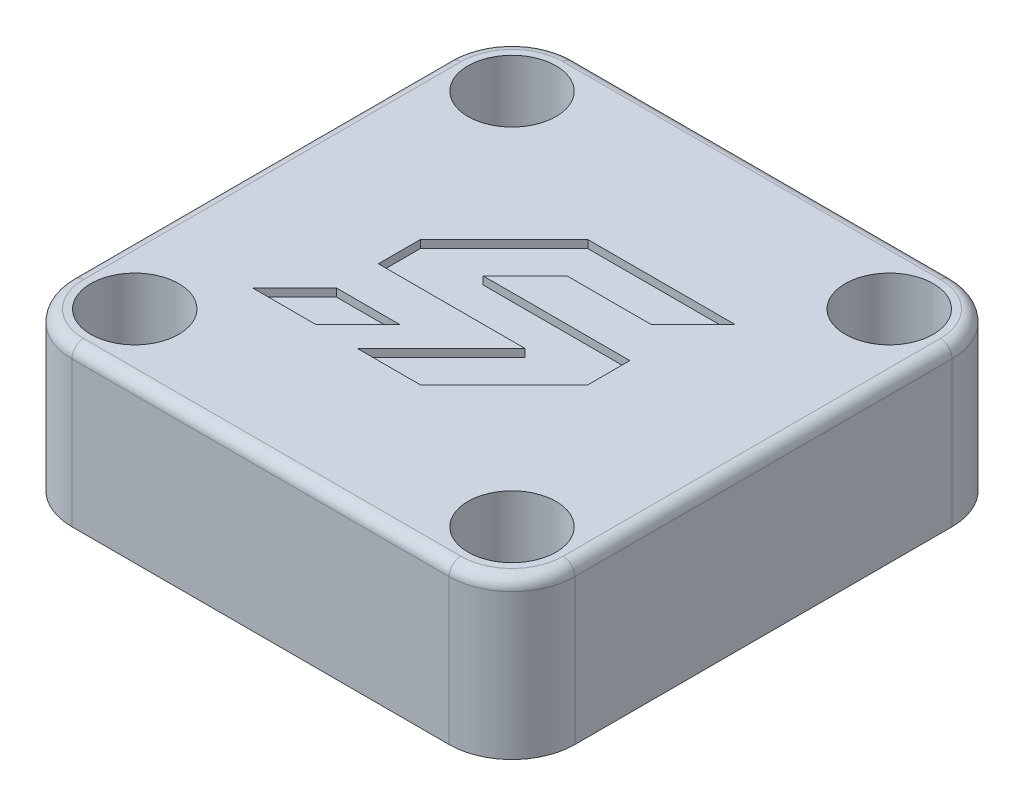
SolidWorks part; units mm, degrees
ref_plane "Front Plane" through (0, 0, 0) normal (0, 0, 1) x (1, 0, 0)
ref_plane "Top Plane" through (0, 0, 0) normal (0, 1, 0) x (1, 0, 0)
ref_plane "Right Plane" through (0, 0, 0) normal (1, 0, 0) x (0, 0, -1)
sketch "Sketch1" plane through (0, 0, 0) normal (0, 1, 0) x (1, 0, 0)
  line L0 (-16, 12) -> (-16, -12)
  line L1 (-12, 12) -> (12, 12)
  line L2 (-12, 12) -> (-12, -12)
  line L3 (-12, -12) -> (12, -12)
  line L4 (12, 12) -> (12, -12)
  line L5 (-12, 12) -> (12, -12) construction
  line L6 (-12, -12) -> (12, 12) construction
  line L7 (-12, -16) -> (12, -16)
  line L8 (16, 12) -> (16, -12)
  line L9 (-12, 16) -> (12, 16)
  circle A0 centre (-12, 12) radius 1.6
  circle A1 centre (12, 12) radius 1.6
  circle A2 centre (12, -12) radius 1.6
  circle A3 centre (-12, -12) radius 1.6
  circle A4 centre (-12, 12) radius 4
  circle A5 centre (12, 12) radius 4
  circle A6 centre (12, -12) radius 4
  circle A7 centre (-12, -12) radius 4
  point P0 (0, 0)
  dimension "D2" = 3.2
  dimension "D3" = 8
  dimension "D1" = 24
extrude "Boss-Extrude1" add sketch "Sketch1" along normal blind 10 contours A5 L9 A4 L1 | L1 A4 L2 A0 | A7 L2 A4 L0 | A7 L3 A3 L2 | A7 L7 A6 L3 | A6 L4 A2 L3 | A6 L8 A5 L4 | A7 L3 A6 L4 A5 L1 A4 L2 | L4 A6 L3 A2 | L3 A7 L2 A3 | L2 A4 L1 A0 | L4 A5 L1 A1 | L1 A5 L4 A1 region at (-14.1072, 0, 0) region at (-14.7484, 0, -14.7484) region at (-14.7484, 0, 9.2516) region at (0, 0, -14.1072) region at (0, 0, 0) region at (-10.1083, 0, -10.1083) region at (0, 0, 14.1072) region at (-10.1083, 0, 10.1083) region at (14.7484, 0, -14.7484) region at (9.2516, 0, 14.7484) region at (14.1072, 0, 0) region at (10.1083, 0, -10.1083) region at (10.1083, 0, 10.1083)
sketch "Sketch2" plane through (0, 0, 0) normal (0, -1, 0) x (1, 0, 0)
  line L0 (-12, 16) -> (12, 16) construction
  line L1 (8, -16) -> (-8, -16)
  line L2 (8, -16) -> (8, 16)
  line L3 (8, 16) -> (-8, 16)
  line L4 (-8, -16) -> (-8, 16)
  line L5 (8, -16) -> (-8, 16) construction
  line L6 (8, 16) -> (-8, -16) construction
  circle A0 centre (0, 0) radius 14
  circle A3 centre (-12, 12) radius 1.6 construction
  circle A4 centre (-12, 12) radius 1.6
  line M12 (-12, -16) -> (12, -16)
  dimension "D1" = 28
  dimension "D2" = 4
extrude "Cut-Extrude1" cut sketch "Sketch2" against normal offset from surface (8.5 mm away) 1.5 contours A0 L4 L2 M12 | A0 region at (0, 0, -14.5009) up to face at (-12, 10, 13.6)
sketch "Sketch3" plane through (0, 10, 0) normal (0, 1, 0) x (1, 0, 0)
  circle A0 centre (-12, 12) radius 2.8
  circle A1 centre (12, 12) radius 2.8
  circle A2 centre (12, -12) radius 2.8
  circle A3 centre (-12, -12) radius 2.8
  dimension "D1" = 5.6
extrude "Cut-Extrude2" cut sketch "Sketch3" against normal offset from surface (8 mm away) 2 up to face at (0, 0, -2.4574)
fillet "Fillet1" radius 3 2 edges at (-8, 4.25, -11.4891) (8, 4.25, -11.4891)
fillet "Fillet2" radius 3 5 edges at (8, 8.5, -14.4807) (8.2775, 8.5, -11.7012) (-8, 8.5, -14.4807) (-8.2775, 8.5, -11.7012) (0, 8.5, 14)
fillet "Fillet3" radius 0.75 8 edges at (-14.8284, 10, 14.8284) (-16, 10, 0) (-14.8284, 10, -14.8284) (0, 10, -16) (14.8284, 10, -14.8284) (16, 10, 0) (14.8284, 10, 14.8284) (0, 10, 16)
sketch "Sketch6" plane through (0, 10, 0) normal (0, 1, 0) x (1, 0, 0)
  line L0 (14.5917, 6.2385) -> (-1.4083, 6.2385)
  line L1 (14.5917, 6.2385) -> (1.2584, -7.0948)
  line L2 (11.9251, 3.5718) -> (-4.0749, 3.5718)
  line L3 (9.2584, 0.9052) -> (-6.7416, 0.9052)
  line L4 (6.5917, -1.7615) -> (-9.4083, -1.7615)
  line L5 (3.9251, -4.4282) -> (-12.0749, -4.4282)
  line L6 (1.2584, -7.0948) -> (-14.7416, -7.0948)
  line L7 (10.5917, 6.2385) -> (-2.7416, -7.0948)
  line L8 (6.5917, 6.2385) -> (-6.7416, -7.0948)
  line L9 (2.5917, 6.2385) -> (-10.7416, -7.0948)
  line L10 (-1.4083, 6.2385) -> (-14.7416, -7.0948)
  line L11 (-6.7416, 0.9052) -> (-6.7416, -1.7615)
  line L12 (6.5917, -1.7615) -> (6.5917, 0.9052)
  line L13 (-6.7416, -1.7615) -> (-6.7416, -4.4282) construction
  line L14 (-6.7416, -4.4282) -> (-9.4083, -7.0948)
  line L15 (-2.7416, -4.4282) -> (-5.4083, -7.0948)
  line L16 (-4.0749, -5.7615) -> (-8.0749, -5.7615) construction
  line L17 (-1.4083, -5.7615) -> (2.5917, -5.7615) construction
  line L18 (5.2584, 3.5718) -> (7.9251, 6.2385)
  dimension "D1" = 16
  dimension "D2" = 45
  dimension "D4" = 2.6667
  dimension "D3" = 6
  dimension "D5" = 5
extrude "Cut-Extrude3" cut sketch "Sketch6" against normal blind 0.5 contours L5 L14 L6 L8 | L15 L5 L8 L6 | L5 L7 L6 L1 | L4 L7 L5 L1 | L4 L12 L3 L7 | L3 L8 L4 L7 | L3 L9 L4 L8 | L3 L11 L4 L9 | L2 L10 L3 L9 | L0 L10 L2 L9 | L0 L9 L2 L8 | L2 L18 L0 L8 region at (5.9251, 10, -4.9052) region at (3.2584, 10, -4.9052) region at (1.9251, 10, 0.4282) region at (5.1473, 10, 0.6504) region at (3.2584, 10, 3.0948) region at (-0.7416, 10, -4.9052) region at (-2.0749, 10, 0.4282) region at (0.5917, 10, 5.7615) region at (-3.4083, 10, -2.2385) region at (-5.2972, 10, 0.206) region at (-6.7416, 10, 5.7615) region at (-4.7416, 10, 5.7615)
equation "\"D4@Sketch6\"=16/6"
